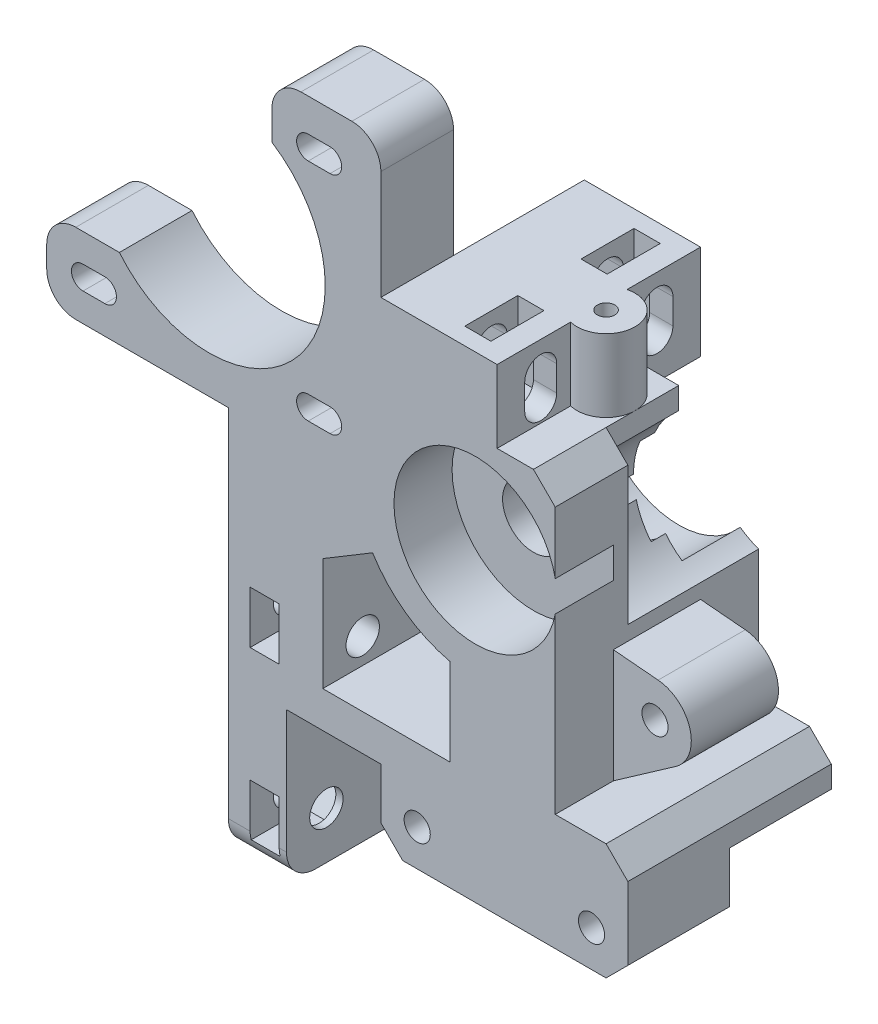
SolidWorks part; units mm, degrees
ref_plane "Front Plane" through (0, 0, 0) normal (0, 0, 1) x (1, 0, 0)
ref_plane "Top Plane" through (0, 0, 0) normal (0, 1, 0) x (1, 0, 0)
ref_plane "Right Plane" through (0, 0, 0) normal (1, 0, 0) x (0, 0, -1)
sketch "Sketch1" plane through (0, 0, 0) normal (0, 0, 1) x (1, 0, 0)
  line L0 (0, 0) -> (0, -11)
  line L1 (0, -11) -> (25, -11)
  line L2 (25, -11) -> (25, -64)
  line L3 (25, -64) -> (33, -64)
  line L4 (33, -64) -> (33, -43)
  line L5 (33, -43) -> (46, -43)
  line L6 (46, -43) -> (46, -53)
  line L7 (46, -53) -> (85, -53)
  line L8 (85, -53) -> (85, -43) construction
  line L9 (85, -43) -> (80, -43)
  line L10 (80, -43) -> (80, -37)
  line L11 (80, -37) -> (70, -37)
  line L12 (70, -37) -> (78.6011, -30.9774)
  line L13 (70, -37) -> (70, -21.361) construction
  line L14 (70, -21.361) -> (76.169, -21.9007)
  line L15 (70, -21.361) -> (70, 12.639)
  line L16 (70, 12.639) -> (46, 12.639)
  line L17 (46, 12.639) -> (46, 31.639)
  line L18 (46, 31.639) -> (31, 31.639)
  line L19 (31, 31.639) -> (31, 23.639)
  line L20 (0, 0) -> (10, 0)
  line L21 (38, -22.5) -> (38, -38)
  line L22 (38, -38) -> (55.5, -38)
  line L23 (55.5, -38) -> (55.5, -26)
  line L24 (38, -22.5) -> (44.8573, -18.3797)
  line L25 (85, -48) -> (46, -48) construction
  line L26 (25, -11) -> (59, -11) construction
  line L27 (5, -5.5) -> (8, -5.5) construction
  line L28 (5, -3.9) -> (8, -3.9)
  line L29 (5, -7.1) -> (8, -7.1)
  line L30 (36, -5.5) -> (39, -5.5) construction
  line L31 (36, -3.9) -> (39, -3.9)
  line L32 (36, -7.1) -> (39, -7.1)
  line L33 (36, 25.5) -> (39, 25.5) construction
  line L34 (36, 27.1) -> (39, 27.1)
  line L35 (36, 23.9) -> (39, 23.9)
  line L36 (5, -5.5) -> (36, -5.5) construction
  line L37 (36, -5.5) -> (36, 25.5) construction
  line L38 (5, -5.5) -> (0, -5.5) construction
  arc A0 (85, -53) -> (85, -43) centre (85, -48) ccw
  circle A1 centre (75.7332, -26.8817) radius 5
  arc A2 (10, 0) -> (31, 23.639) centre (22.3388, 10.186) ccw
  arc A3 (44.8573, -18.3797) -> (55.5, -26) centre (59.3127, -9.4331) ccw
  circle A4 centre (51, -48) radius 1.8
  circle A5 centre (75, -48) radius 1.8
  circle A6 centre (85, -48) radius 1.8
  circle A7 centre (75.7332, -26.8817) radius 1.8
  circle A8 centre (59, -11) radius 4.25
  arc A9 (5, -3.9) -> (5, -7.1) centre (5, -5.5) ccw
  arc A10 (8, -7.1) -> (8, -3.9) centre (8, -5.5) ccw
  arc A11 (36, -3.9) -> (36, -7.1) centre (36, -5.5) ccw
  arc A12 (39, -7.1) -> (39, -3.9) centre (39, -5.5) ccw
  arc A13 (36, 27.1) -> (36, 23.9) centre (36, 25.5) ccw
  arc A14 (39, 23.9) -> (39, 27.1) centre (39, 25.5) ccw
  point P45 (6.5, -5.5)
  point P50 (37.5, -5.5)
  point P57 (37.5, 25.5)
  dimension "D1" = 11
  dimension "D14" = 35
  dimension "D9" = 10
  dimension "D15" = 10
  dimension "D21" = 10
  dimension "D28" = 17
  dimension "D31" = 3.6
  dimension "D33" = 24
  dimension "D34" = 34
  dimension "D35" = 8.5
  dimension "D37" = 1.6
  dimension "D39" = 5
  dimension "D40" = 16
  dimension "D2" = 25
  dimension "D4" = 8
  dimension "D5" = 21
  dimension "D6" = 13
  dimension "D7" = 10
  dimension "D8" = 39
  dimension "D10" = 5
  dimension "D11" = 6
  dimension "D12" = 10
  dimension "D13" = 10.5
  dimension "D16" = 40
  dimension "D17" = 34
  dimension "D18" = 24
  dimension "D19" = 19
  dimension "D20" = 15
  dimension "D22" = 8
  dimension "D23" = 15.5
  dimension "D24" = 17.5
  dimension "D25" = 12
  dimension "D26" = 8
  dimension "D27" = 121
  dimension "D29" = 5
  dimension "D30" = 5
  dimension "D32" = 5
  dimension "D36" = 3
  dimension "D38" = 31
  dimension "D41" = 53
extrude "Boss-Extrude1" add sketch "Sketch1" against normal blind 34 contours A2 L20 L0 L1 L2 L3 L4 L5 L6 L7 A0 L9 L10 L11 L12 A1 L14 L15 L16 L17 L18 L19 A14 L35 A13 L34 A12 L32 A11 L31 A10 L29 A9 L28 A8 A6 A5 A4 L24 A3 L23 L22 L21 | A1 A7 region at (48.0686, -19.084, 0) region at (79.3153, -23.5993, 0)
sketch "Sketch7" plane through (0, 0, 0) normal (0, 0, 1) x (1, 0, 0)
  line L1 (70, -21.361) -> (80.7332, -21.361)
  line L2 (70, -21.361) -> (70, -37)
  line L3 (70, -37) -> (80.7332, -37)
  line L4 (80.7332, -21.361) -> (80.7332, -37)
  circle A0 centre (59, -11) radius 11.2
  arc A1 (78.6011, -30.9774) -> (76.169, -21.9007) centre (75.7332, -26.8817) ccw construction
  dimension "D1" = 22.4
extrude "Cut-Extrude5" cut sketch "Sketch7" against normal blind 8
sketch "Sketch2" plane through (25, 0, 0) normal (-1, 0, 0) x (0, 0, 1)
  line L0 (-28.5, -34.5) -> (-5.5, -34.5) construction
  line L1 (-5.5, -34.5) -> (-5.5, -57.5) construction
  line L2 (-5.5, -57.5) -> (-28.5, -57.5) construction
  line L3 (-28.5, -57.5) -> (-28.5, -34.5) construction
  line L4 (-17, -57.5) -> (-17, -64) construction
  line L5 (-34, -64) -> (0, -64) construction
  line L6 (-34, -24) -> (-28, -24)
  line L7 (-34, -11) -> (-34, -64) construction
  line L8 (-28, -24) -> (-28, 13.5)
  line L9 (-28, 13.5) -> (-10, 13.5)
  line L10 (-10, 13.5) -> (-10, 31.639)
  line L11 (-34, 31.639) -> (0, 31.639) construction
  line L12 (-10, 31.639) -> (-34, 31.639)
  line L13 (-34, 31.639) -> (-34, -24)
  circle A0 centre (-28.5, -34.5) radius 2.3
  circle A1 centre (-5.5, -34.5) radius 2.3
  circle A2 centre (-5.5, -57.5) radius 2.3
  circle A3 centre (-28.5, -57.5) radius 2.3
  dimension "D3" = 4.6
  dimension "D1" = 23
  dimension "D2" = 6.5
  dimension "D4" = 6
  dimension "D5" = 37.5
  dimension "D6" = 18
  dimension "D7" = 40
extrude "Cut-Extrude1" cut sketch "Sketch2" against normal blind 28
sketch "Sketch4" plane through (0, 0, -34) normal (0, 0, -1) x (-1, 0, 0)
  line L0 (-25, -24) -> (-46, -11.3806)
  line L1 (-46, -11.3806) -> (-46, 31.639)
  line L2 (-46, 31.639) -> (0, 31.639)
  line L3 (0, 31.639) -> (0, -11)
  line L4 (0, -11) -> (-25, -11)
  line L5 (-25, -11) -> (-25, -24)
  line L6 (-70, 12.639) -> (-67, 12.639)
  line L7 (-46, -53) -> (-85, -53) construction
  line L8 (-70, 12.639) -> (-70, -19.361)
  line L9 (-70, -21.361) -> (-70, 12.639) construction
  line L10 (-80, -43) -> (-90, -43)
  line L11 (-67, 12.639) -> (-67, -0.361)
  line L12 (-80, -43) -> (-80, -53)
  line L13 (-80, -53) -> (-90, -53)
  line L14 (-90, -43) -> (-90, -53)
  arc A0 (-70, -19.361) -> (-67, -0.361) centre (-73.7732, -9.0284) ccw
  arc A1 (-85, -43) -> (-85, -53) centre (-85, -48) ccw construction
  dimension "D4" = 11
  dimension "D1" = 24.5
  dimension "D2" = 3
  dimension "D3" = 32
  dimension "D5" = 13
extrude "Cut-Extrude2" cut sketch "Sketch4" against normal blind 24
sketch "Sketch5" plane through (0, 0, -34) normal (0, 0, -1) x (-1, 0, 0)
  line L0 (-33, -24) -> (-33, -64)
  line L1 (-25, -24) -> (-38, -24) construction
  line L2 (-33, -24) -> (0, -24)
  line L3 (0, -24) -> (0, 31.639)
  line L4 (0, 31.639) -> (-90, 31.639)
  line L5 (-90, 31.639) -> (-90, -64)
  line L6 (-90, -64) -> (-33, -64)
  line L7 (-46, 31.639) -> (-31, 31.639) construction
  line L9 (-25, -64) -> (-33, -64) construction
  line L10 (-33, -64) -> (-33, -43) construction
  arc A0 (-85, -43) -> (-85, -53) centre (-85, -48) ccw construction
extrude "Cut-Extrude3" cut sketch "Sketch5" against normal blind 6 contours L5 L6 L0 L2 L3 L4
sketch "Sketch6" plane through (0, 0, -34) normal (0, 0, -1) x (-1, 0, 0)
  line L0 (-67, 12.639) -> (-67, -3.4502)
  line L1 (-70, -21.361) -> (-80.7332, -21.361)
  line L2 (-70, -21.361) -> (-70, -37)
  line L3 (-70, -37) -> (-80.7332, -37)
  line L4 (-80.7332, -21.361) -> (-80.7332, -37)
  line L5 (-67, -0.361) -> (-67, 12.639) construction
  line L6 (-67, 12.639) -> (-62, 12.639)
  line L7 (-46, 12.639) -> (-67, 12.639) construction
  line L8 (-62, 12.639) -> (-62, -0.417)
  circle A0 centre (-59, -11) radius 11
  arc A1 (-76.169, -21.9007) -> (-78.6011, -30.9774) centre (-75.7332, -26.8817) ccw construction
  dimension "D1" = 22
  dimension "D2" = 5
extrude "Cut-Extrude4" cut sketch "Sketch6" against normal blind 14 contours A0 L8 L6 L0 | A0 | L1 L4 L3 L2 region at (64.5868, 5.4811, -34) region at (59, -11, -34) region at (75.3666, -29.1805, -34)
sketch "Sketch8" plane through (0, 0, -28) normal (0, 0, -1) x (-1, 0, 0)
  line L1 (-46, -53) -> (-80, -53)
  line L2 (-46, -53) -> (-46, -43)
  line L3 (-46, -43) -> (-80, -43)
  line L4 (-80, -53) -> (-80, -43)
extrude "Cut-Extrude7" cut sketch "Sketch8" against normal blind 14
sketch "Sketch9" plane through (0, 0, -20) normal (0, 0, -1) x (-1, 0, 0)
  circle A0 centre (-59, -11) radius 7.9
  dimension "D1" = 15.8
extrude "Cut-Extrude8" cut sketch "Sketch9" against normal blind 2
sketch "Sketch10" plane through (0, 12.639, 0) normal (0, 1, 0) x (1, 0, 0)
  line L0 (70, 10) -> (70, 0)
  line L1 (70, 8) -> (70, 0) construction
  line L2 (57, 2.35) -> (57, 0) construction
  line L3 (55.2, 25.65) -> (58.8, 25.65)
  line L4 (55.2, 25.65) -> (55.2, 18.35)
  line L5 (55.2, 18.35) -> (58.8, 18.35)
  line L6 (58.8, 25.65) -> (58.8, 18.35)
  line L7 (55.2, 9.65) -> (58.8, 9.65)
  line L8 (55.2, 9.65) -> (55.2, 2.35)
  line L9 (55.2, 2.35) -> (58.8, 2.35)
  line L10 (58.8, 9.65) -> (58.8, 2.35)
  line L11 (57, 25.65) -> (57, 28) construction
  line L12 (57, 9.65) -> (57, 18.35) construction
  line L14 (70, 0) -> (46, 0) construction
  line L15 (70, 10) -> (67, 10)
  line L16 (67, 10) -> (67, 20)
  line L17 (67, 20) -> (62, 20)
  line L18 (67.4569, 20) -> (48, 20) construction
  line L19 (62, 20) -> (62, 17.873)
  line L20 (62, 17.873) -> (62, 10.127) construction
  line L21 (63, 14) -> (57, 14) construction
  line L22 (70, 0) -> (62, 0)
  line L23 (62, 0) -> (62, 10.127)
  line L24 (46, 28) -> (62, 28) construction
  arc A0 (62, 17.873) -> (62, 10.127) centre (63, 14) cw
  line M9 (67, 20) -> (62, 20)
  line M15 (70, 0) -> (70, 10)
  line M16 (70, 10) -> (67, 10)
  line M17 (67, 10) -> (67, 20)
  dimension "D5" = 4
  dimension "D2" = 7.3
  dimension "D3" = 3.6
  dimension "D4" = 2.35
  dimension "D6" = 5
extrude "Cut-Extrude9" cut sketch "Sketch10" against normal blind 10 contours L6 L3 L4 L5 | L19 A0 L16 M9 | A0 L23 L22 M17 M15 M16 | L8 L9 L10 L7 region at (64.9023, 12.639, -18.5143) region at (66.0025, 12.639, -5.245) region at (57, 12.639, -22)
sketch "Sketch11" plane through (0, -53, 0) normal (0, -1, 0) x (1, 0, 0)
  line L0 (46, -14) -> (80, -14) construction
  circle A0 centre (63, -14) radius 1.2
  dimension "D1" = 2.4
extrude "Cut-Extrude10" cut sketch "Sketch11" against normal through all both and the other way through all
sketch "Sketch12" plane through (0, -53, 0) normal (0, -1, 0) x (1, 0, 0)
  circle A0 centre (63, -14) radius 8.1
  dimension "D1" = 16.2
extrude "Cut-Extrude11" cut sketch "Sketch12" against normal up to surface (10 mm away) from offset 6 up to face at (55.5, -43, -14.15) offset against normal yes
sketch "Sketch13" plane through (0, -53, 0) normal (0, -1, 0) x (1, 0, 0)
  circle A0 centre (63, -14) radius 6.1
  dimension "D1" = 12.2
extrude "Cut-Extrude12" cut sketch "Sketch13" against normal up to surface (6 mm away) up to face at (63, -47, -11.675)
sketch "Sketch15" plane through (62, 0, 0) normal (1, 0, 0) x (0, 0, -1)
  line L0 (6, 8.639) -> (6, 5.139) construction
  line L1 (8.2, 8.639) -> (8.2, 5.139)
  line L2 (3.8, 8.639) -> (3.8, 5.139)
  line L3 (22, 8.639) -> (22, 5.139) construction
  line L4 (24.2, 8.639) -> (24.2, 5.139)
  line L5 (19.8, 8.639) -> (19.8, 5.139)
  line L6 (6, 6.889) -> (22, 6.889) construction
  line L7 (6, 8.639) -> (6, 12.639) construction
  line L9 (10, 12.639) -> (0, 12.639) construction
  line L10 (10, 12.639) -> (10, 2.639) construction
  arc A0 (8.2, 8.639) -> (3.8, 8.639) centre (6, 8.639) ccw
  arc A1 (3.8, 5.139) -> (8.2, 5.139) centre (6, 5.139) ccw
  arc A2 (24.2, 8.639) -> (19.8, 8.639) centre (22, 8.639) ccw
  arc A3 (19.8, 5.139) -> (24.2, 5.139) centre (22, 5.139) ccw
  point P2 (6, 6.889)
  point P11 (22, 6.889)
  dimension "D2" = 2.2
  dimension "D1" = 3.5
  dimension "D3" = 4
  dimension "D4" = 16
  dimension "D5" = 4
extrude "Cut-Extrude14" cut sketch "Sketch15" against normal up to surface (16 mm away) up to face at (46, 0.6292, -19)
ref_plane "Plane1" through (28, 0, 0) normal (-1, 0, 0) x (0, 0, 1)
sketch "Sketch16" plane through (28, 0, 0) normal (-1, 0, 0) x (0, 0, 1)
  line L0 (-30.5785, -53.9) -> (-34, -53.9)
  line L1 (-24.3431, -34.5) -> (-26.4215, -30.9)
  line L2 (-26.4215, -30.9) -> (-30.5785, -30.9)
  line L3 (-30.5785, -30.9) -> (-32.6569, -34.5)
  line L4 (-32.6569, -34.5) -> (-30.5785, -38.1)
  line L5 (-30.5785, -38.1) -> (-26.4215, -38.1)
  line L6 (-26.4215, -38.1) -> (-24.3431, -34.5)
  line L7 (-24.3431, -57.5) -> (-26.4215, -53.9)
  line L8 (-26.4215, -53.9) -> (-30.5785, -53.9)
  line L9 (-30.5785, -53.9) -> (-32.6569, -57.5)
  line L10 (-32.6569, -57.5) -> (-30.5785, -61.1)
  line L11 (-30.5785, -61.1) -> (-26.4215, -61.1)
  line L12 (-26.4215, -61.1) -> (-24.3431, -57.5)
  line L13 (-9.6569, -57.5) -> (-7.5785, -61.1)
  line L14 (-7.5785, -61.1) -> (-3.4215, -61.1)
  line L15 (-3.4215, -61.1) -> (-1.3431, -57.5)
  line L16 (-1.3431, -57.5) -> (-3.4215, -53.9)
  line L17 (-3.4215, -53.9) -> (-7.5785, -53.9)
  line L18 (-7.5785, -53.9) -> (-9.6569, -57.5)
  line L19 (-9.6569, -34.5) -> (-7.5785, -38.1)
  line L20 (-7.5785, -38.1) -> (-3.4215, -38.1)
  line L21 (-3.4215, -38.1) -> (-1.3431, -34.5)
  line L22 (-1.3431, -34.5) -> (-3.4215, -30.9)
  line L23 (-3.4215, -30.9) -> (-7.5785, -30.9)
  line L24 (-7.5785, -30.9) -> (-9.6569, -34.5)
  line L25 (-34, -24) -> (-34, -64) construction
  line L26 (-34, -53.9) -> (-34, -61.1)
  line L27 (-34, -61.1) -> (-30.5785, -61.1)
  line L28 (-30.5785, -30.9) -> (-34, -30.9)
  line L29 (-34, -30.9) -> (-34, -38.1)
  line L30 (-34, -38.1) -> (-30.5785, -38.1)
  line L31 (-3.4215, -30.9) -> (0, -30.9)
  line L32 (0, -11) -> (0, -64) construction
  line L33 (0, -30.9) -> (0, -38.1)
  line L34 (0, -38.1) -> (-3.4215, -38.1)
  line L35 (-3.4215, -53.9) -> (0, -53.9)
  line L36 (0, -53.9) -> (0, -61.1)
  line L37 (0, -61.1) -> (-3.4215, -61.1)
  circle A0 centre (-28.5, -34.5) radius 3.6 construction
  circle A1 centre (-28.5, -57.5) radius 3.6 construction
  circle A2 centre (-5.5, -57.5) radius 3.6 construction
  circle A3 centre (-5.5, -34.5) radius 3.6 construction
  dimension "D1" = 7.2
extrude "Cut-Extrude15" cut sketch "Sketch16" against normal blind 4 contours L29 L30 L4 L3 L28 | L5 L6 L1 L2 L3 L4 | L26 L27 L10 L9 L0 | L11 L12 L7 L8 L9 L10 | L23 L24 L19 L20 L21 L22 | L34 L33 L31 L22 L21 | L17 L18 L13 L14 L15 L16 | L37 L36 L35 L16 L15 region at (28, -57.5, -32.7333) region at (28, -57.5, -28.5) region at (28, -34.5, -28.5) region at (28, -34.5, -32.7333) region at (28, -57.5, -5.5) region at (28, -57.5, -1.2667) region at (28, -34.5, -5.5) region at (28, -34.5, -1.2667)
fillet "Fillet1" radius 4 7 edges at (31, 31.639, -5) (46, 31.639, -5) (0, 0, -5) (0, -11, -5) (29, -24, -34) (29, -64, -34) (29, -64, 0)
sketch "Sketch17" plane through (0, 0, -10) normal (0, 0, -1) x (-1, 0, 0)
  line L0 (-80, -43) -> (-85, -43) construction
  line L1 (-80, -53) -> (-90, -53)
  line L2 (-80, -53) -> (-80, -43)
  line L3 (-80, -43) -> (-90, -43)
  line L4 (-90, -53) -> (-90, -43)
  arc A0 (-85, -43) -> (-85, -53) centre (-85, -48) ccw construction
extrude "fail" cut sketch "Sketch17" against normal through all both and the other way through all
chamfer "Chamfer1" distance 3 angle 45 4 edges at (46, -53, -7) (80, -53, -7) (70, 2.639, -5) (80, -37, -14)
